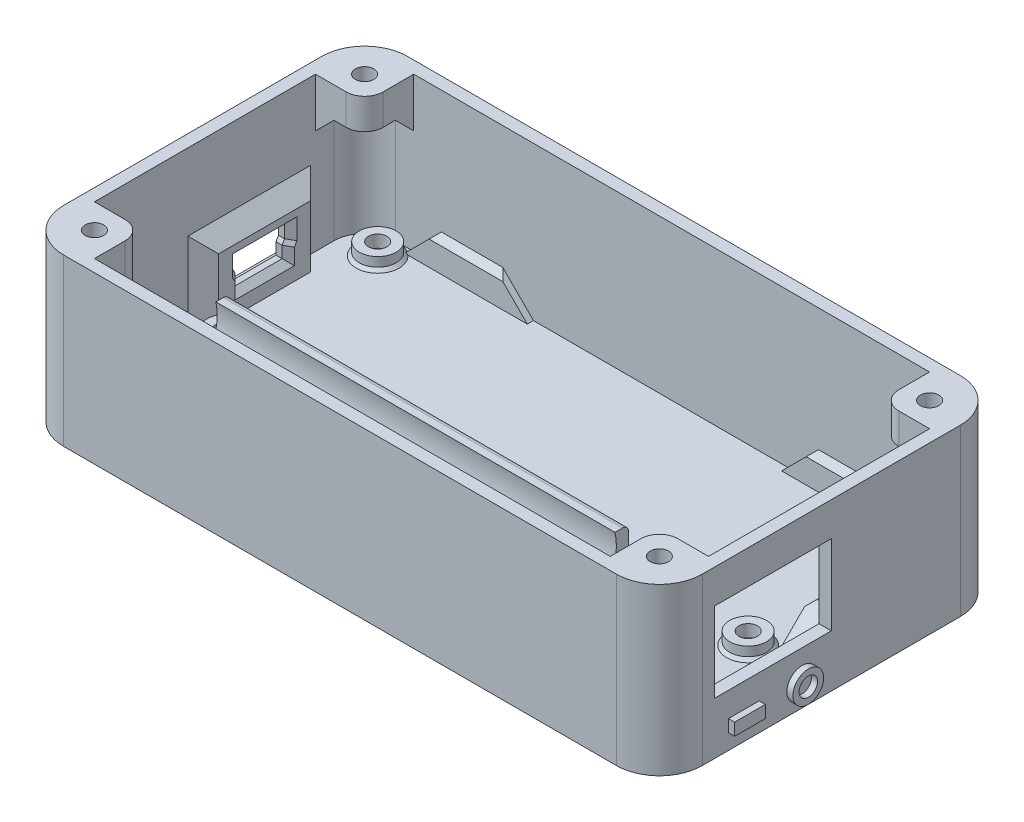
SolidWorks part; units mm, degrees
ref_plane "Front Plane" through (0, 0, 0) normal (0, 0, 1) x (1, 0, 0)
ref_plane "Top Plane" through (0, 0, 0) normal (0, 1, 0) x (1, 0, 0)
ref_plane "Right Plane" through (0, 0, 0) normal (1, 0, 0) x (0, 0, -1)
sketch "Sketch1" plane through (0, 0, 0) normal (0, 1, 0) x (1, 0, 0)
  line L0 (-45, 28) -> (45, 28)
  line L1 (-45, -26) -> (45, -26)
  line L2 (-50, -21) -> (-50, 21)
  line L3 (-45, 26) -> (45, 26)
  line L4 (50, -21) -> (50, 21)
  line L5 (-50, -26) -> (50, 26) construction
  line L6 (-50, 26) -> (50, -26) construction
  line L7 (52, -21) -> (52, 21)
  line L8 (-45, -28) -> (45, -28)
  line L9 (-52, -21) -> (-52, 21)
  arc A0 (-50, -21) -> (-45, -26) centre (-45, -21) ccw
  arc A1 (50, -21) -> (45, -26) centre (45, -21) cw
  arc A2 (50, 21) -> (45, 26) centre (45, 21) ccw
  arc A3 (-45, 26) -> (-50, 21) centre (-45, 21) ccw
  arc A4 (52, 21) -> (45, 28) centre (45, 21) ccw
  arc A5 (52, -21) -> (45, -28) centre (45, -21) cw
  arc A6 (-52, -21) -> (-45, -28) centre (-45, -21) ccw
  arc A7 (-45, 28) -> (-52, 21) centre (-45, 21) ccw
  point P0 (0, 0)
  dimension "D3" = 5
  dimension "D1" = 100
  dimension "D2" = 52
  dimension "D4" = 2
extrude "Boss-Extrude1" add sketch "Sketch1" along normal blind 2 contours L9 A7 L0 A4 L7 A5 L8 A6
extrude "Boss-Extrude2" add sketch "Sketch1<3>" along normal blind 27
sketch "Sketch1<3>" plane through (0, 0, 0) normal (0, 1, 0) x (1, 0, 0) same geometry as "Sketch1"
sketch "Sketch2" plane through (-52, 0, 0) normal (-1, 0, 0) x (0, 0, 1)
  line L0 (-28, 2) -> (28, 2) construction
  line L1 (-28, 27) -> (-28, 0) construction
  line L2 (28, 27) -> (28, 0) construction
  line L3 (21, 0) -> (-21, 0) construction
  line L4 (-28, 5.6) -> (28, 5.6) construction
  line L5 (-26, 0) -> (-26, 27) construction
  line L6 (-28, 0) -> (-21, 0) construction
  line L7 (-21, 27) -> (-28, 27) construction
  line L8 (-11.07, 7.9) -> (-3.37, 7.9) construction
  line L9 (-11.07, 5.6) -> (-3.37, 5.6) construction
  line L10 (-11.07, 5.6) -> (-11.07, 9.5) construction
  line L11 (-11.07, 9.5) -> (-3.37, 9.5) construction
  line L12 (-3.37, 5.6) -> (-3.37, 9.5) construction
  line L13 (-11.07, 5.6) -> (-3.37, 9.5) construction
  line L14 (-11.07, 9.5) -> (-3.37, 5.6) construction
  line L19 (-3.77, 5.6) -> (-10.67, 5.6) construction
  line L20 (-3.77, 5.6) -> (-3.77, 9.5) construction
  line L21 (-3.77, 9.5) -> (-10.67, 9.5) construction
  line L22 (-10.67, 5.6) -> (-10.67, 9.5) construction
  line L23 (-3.77, 5.6) -> (-10.67, 9.5) construction
  line L24 (-3.77, 9.5) -> (-10.67, 5.6) construction
  line L25 (-11.07, 7.2) -> (-3.37, 7.2) construction
  line L26 (-11.07, 9.5) -> (-11.07, 7.9) construction
  line L27 (-11.07, 7.9) -> (-10.67, 7.2) construction
  line L28 (-10.67, 7.2) -> (-10.67, 5.6) construction
  line L29 (-10.67, 5.6) -> (-3.77, 5.6) construction
  line L30 (-3.77, 5.6) -> (-3.77, 7.2) construction
  line L31 (-3.77, 7.2) -> (-3.37, 7.9) construction
  line L32 (-3.37, 7.9) -> (-3.37, 9.5) construction
  line L33 (-3.37, 9.5) -> (-11.07, 9.5) construction
  line L34 (-28, 4) -> (28, 4) construction
  line L35 (-2.97, 9.9) -> (-11.47, 9.9)
  line L36 (-11.47, 9.9) -> (-11.47, 7.7938)
  line L37 (-11.47, 7.7938) -> (-11.07, 7.0938)
  line L38 (-11.07, 7.0938) -> (-11.07, 5.2)
  line L39 (-11.07, 5.2) -> (-3.37, 5.2)
  line L40 (-3.37, 5.2) -> (-3.37, 7.0938)
  line L41 (-3.37, 7.0938) -> (-2.97, 7.7938)
  line L42 (-2.97, 7.7938) -> (-2.97, 9.9)
  line L43 (-14.72, 3.05) -> (-14.72, 2)
  line L44 (0.28, 3.05) -> (-14.72, 3.05) construction
  line L45 (0.28, 3.05) -> (0.28, 12.05)
  line L46 (0.28, 12.05) -> (-14.72, 12.05)
  line L47 (-14.72, 3.05) -> (-14.72, 12.05)
  line L48 (0.28, 3.05) -> (-14.72, 12.05) construction
  line L49 (0.28, 12.05) -> (-14.72, 3.05) construction
  line L50 (-14.72, 2) -> (0.28, 2)
  line L51 (0.28, 2) -> (0.28, 3.05)
  line L52 (-14.72, 3.05) -> (0.28, 3.05)
  point P20 (-7.22, 7.55)
  point P21 (-7.22, 7.55)
  point P22 (-7.22, 7.55)
  point P43 (-7.22, 7.55)
  dimension "D1" = 2
  dimension "D3" = 2
  dimension "D4" = 7.7
  dimension "D5" = 3.9
  dimension "D6" = 6.9
  dimension "D7" = 1.6
  dimension "D8" = 1.6
  dimension "D2" = 2
  dimension "D9" = 1.6
  dimension "D10" = 18.78
  dimension "D12" = 9
  dimension "D13" = 15
  dimension "D11" = 0.4
extrude "Boss-Extrude3" add sketch "Sketch2" against normal blind 4.5 contours L52 L43 L50 L51 | L47 L52 L45 L46 L42 L41 L40 L39 L38 L37 L36 L35 region at (-52, 2.525, -7.22) region at (-52, 7.55, -14.5451)
extrude "Cut-Extrude1" cut sketch "Sketch2<2>" against normal blind 4.5 contours L41 L42 L35 L36 L37 L38 L39 L40 region at (-52, 7.6073, -7.22)
sketch "Sketch2<2>" plane through (-52, 0, 0) normal (-1, 0, 0) x (0, 0, 1) same geometry as "Sketch2"
fillet "Chamfer1" radius 2.5 3 edges at (-50, 7.025, 0.28) (-50, 12.05, -7.22) (-50, 7.025, -14.72) type face fillet profile chamfer first side face at (-48.75, 7.025, -14.72) first side face at (-48.75, 7.025, 0.28) first side face at (-48.75, 12.05, -7.22) second side face at (-50, 10.7625, -3.61)
chamfer "Chamfer2" distance 1 angle 45 8 edges at (-47.5, 8.8469, -2.97) (-47.5, 7.4438, -3.17) (-47.5, 6.1469, -3.37) (-47.5, 9.9, -7.22) (-47.5, 8.8469, -11.47) (-47.5, 7.4438, -11.27) (-47.5, 6.1469, -11.07) (-47.5, 5.2, -7.22)
extrude "Cut-Extrude3" cut sketch "Sketch2<5>" against normal blind 2.5 contours L47 L52 L45 L46 L42 L41 L40 L39 L38 L37 L36 L35 region at (-52, 7.55, -14.5451)
sketch "Sketch2<5>" plane through (-52, 0, 0) normal (-1, 0, 0) x (0, 0, 1) same geometry as "Sketch2"
sketch "Sketch3" plane through (0, 2, 0) normal (0, 1, 0) x (1, 0, 0)
  line L0 (-45, 26) -> (45, 26) construction
  line L1 (-47.5, 25) -> (43.9, 25) construction
  line L2 (-47.5, 25) -> (-47.5, -5.5) construction
  line L3 (-47.5, -5.5) -> (43.9, -5.5) construction
  line L4 (43.9, 25) -> (43.9, -5.5) construction
  line L5 (-47.5, 25) -> (43.9, -5.5) construction
  line L6 (-47.5, -5.5) -> (43.9, 25) construction
  line L8 (-50, 17.22) -> (-50, 21) construction
  line L10 (-37.5, 25) -> (-27.5, 25)
  line L11 (-37.5, 25) -> (-37.5, 26)
  line L12 (-37.5, 26) -> (-27.5, 26)
  line L13 (-27.5, 25) -> (-27.5, 26)
  line L14 (-37.5, 25) -> (-27.5, 26) construction
  line L15 (-37.5, 26) -> (-27.5, 25) construction
  line L16 (23.9, 25) -> (33.9, 25)
  line L17 (23.9, 25) -> (23.9, 26)
  line L18 (23.9, 26) -> (33.9, 26)
  line L19 (33.9, 25) -> (33.9, 26)
  line L20 (23.9, 25) -> (33.9, 26) construction
  line L21 (23.9, 26) -> (33.9, 25) construction
  line L26 (50, -21) -> (50, 21) construction
  line L27 (43.9, 4.75) -> (50, 4.75)
  line L28 (43.9, 4.75) -> (43.9, 14.75)
  line L29 (43.9, 14.75) -> (50, 14.75)
  line L30 (50, 4.75) -> (50, 14.75)
  line L31 (43.9, 4.75) -> (50, 14.75) construction
  line L32 (43.9, 14.75) -> (50, 4.75) construction
  circle A0 centre (-44.33, 22.46) radius 1.5
  circle A1 centre (40.76, 22.46) radius 1.5
  circle A2 centre (40.76, -2.31) radius 1.5
  circle A3 centre (-44.33, -2.31) radius 1.5
  circle A4 centre (-44.33, 22.46) radius 3
  circle A5 centre (-44.33, -2.31) radius 3
  circle A6 centre (40.76, -2.31) radius 3
  circle A7 centre (40.76, 22.46) radius 3
  point P4 (-1.8, 9.75)
  point P29 (-32.5, 25.5)
  point P34 (28.9, 25.5)
  point P39 (46.95, 9.75)
  line M20 (50, -21) -> (50, 21)
  dimension "D11" = 3
  dimension "D12" = 3
  dimension "D13" = 3
  dimension "D14" = 3
  dimension "D1" = 1
  dimension "D2" = 2.5
  dimension "D3" = 91.4
  dimension "D4" = 30.5
  dimension "D5" = 3.17
  dimension "D6" = 2.54
  dimension "D7" = 85.09
  dimension "D8" = 24.77
  dimension "D9" = 85.09
  dimension "D10" = 24.77
  dimension "D16" = 10
  dimension "D17" = 10
  dimension "D18" = 10
  dimension "D19" = 10
  dimension "D20" = 10
  dimension "D15" = 1.5
extrude "Boss-Extrude4" add sketch "Sketch3" along normal blind 2 contours A4 | A0 | A3 | A5 | A2 | A6 | A1 | A7
extrude "Boss-Extrude5" add sketch "Sketch3<3>" along normal blind 5 contours L29 L28 L27 M20 | L12 L13 L10 L11 | L16 L19 L18 L17 region at (46.95, 2, -9.75)
sketch "Sketch3<3>" plane through (0, 2, 0) normal (0, 1, 0) x (1, 0, 0) same geometry as "Sketch3"
chamfer "Chamfer3" distance 5 angle 45 6 edges at (46.95, 2, -4.75) (46.95, 2, -14.75) (33.9, 2, -25.5) (-37.5, 2, -25.5) (-27.5, 2, -25.5) (23.9, 2, -25.5)
chamfer "Chamfer4" distance 0.5 angle 45 4 edges at (40.76, 2, 5.31) (40.76, 2, -19.46) (-44.33, 2, -19.46) (-44.33, 2, 5.31)
chamfer "Chamfer5" distance 1 angle 45 3 edges at (-32.5, 7, -25) (43.9, 7, -9.75) (28.9, 7, -25)
ref_plane "Plane1" through (-40, 0, 0) normal (1, 0, 0) x (0, 0, -1)
sketch "Sketch7" plane through (-40, 0, 0) normal (1, 0, 0) x (0, 0, -1)
  line L0 (-26, 27) -> (-26, 2) construction
  line L1 (-21, 2) -> (-26, 2) construction
  line L2 (-0.25, 2) -> (-21, 2) construction
  line L3 (-26, 27) -> (-26, 2) construction
  line L4 (-21, 2) -> (-26, 2) construction
  line L5 (-0.25, 2) -> (-6, 2) construction
  line L7 (-12.6717, 2) -> (-26, 2)
  line L8 (-9, 2) -> (-12.6717, 2)
  line L9 (-6, 7.6667) -> (-6, 12)
  line L10 (-7, 13) -> (-8.225, 13)
  line L12 (-6, 2) -> (-12.6717, 13) construction
  line L13 (-6, 13) -> (-12.6717, 2) construction
  line L15 (-26, 11) -> (-26, 16)
  line L18 (-26, 11) -> (-23.2203, 16) construction
  line L19 (-26, 16) -> (-23.2203, 11) construction
  line L20 (-26, 2) -> (-26, 16)
  line L21 (-9, 2) -> (-7, 4.6667)
  line L22 (-9, 2) -> (-21, 2) construction
  line L23 (-24.4833, 16) -> (-26, 19)
  line L24 (-26, 19) -> (-26, 16)
  line L25 (-26, 16) -> (-24.4833, 16) construction
  arc A0 (-24.4833, 16) -> (-8.225, 13) centre (-17, 11) ccw
  arc A1 (-7, 4.6667) -> (-6, 7.6667) centre (-11, 7.6667) ccw
  arc A2 (-7, 13) -> (-6, 12) centre (-7, 12) cw
  point P10 (-9.3359, 7.5)
  point P15 (-24.6101, 13.5)
  point P21 (-6, 6)
  dimension "D1" = 18
  dimension "D9" = 5
  dimension "D10" = 1
  dimension "D2" = 9
  dimension "D3" = 9
  dimension "D4" = 20
  dimension "D5" = 11
  dimension "D6" = 5
  dimension "D7" = 3
  dimension "D8" = 4
  dimension "D11" = 3
extrude "Boss-Extrude6" add sketch "Sketch7" along normal blind 65 contours A2 L10 A0 L7 L8 L21 A1 L9 | A0 L20 L7 | A0 L15 region at (-40, 15.848, 25.5244) region at (-40, 4.0103, 23.9897) region at (-40, 6.4212, 8.6012)
fillet "Fillet1" radius 0.5 1 edges at (-7.5, 2, 9)
sketch "Sketch8" plane through (52, 0, 0) normal (1, 0, 0) x (0, 0, -1)
  line L0 (-19, 27) -> (-19, 0) construction
  line L1 (-21, 27) -> (21, 27) construction
  line L2 (-21, 0) -> (21, 0) construction
  line L3 (-21, 27) -> (-21, 0) construction
  line L4 (-19, 21.5) -> (0, 21.5)
  line L5 (-19, 21.5) -> (-19, 8.5)
  line L6 (-19, 8.5) -> (0, 8.5)
  line L7 (0, 21.5) -> (0, 8.5)
  line L8 (-19, 21.5) -> (0, 8.5) construction
  line L9 (-19, 8.5) -> (0, 21.5) construction
  line L10 (-21, 13) -> (-6.5081, 13) construction
  line L12 (-19, 3.5) -> (-9.5, 3.5) construction
  line L13 (-9.5, 3.5) -> (0, 3.5) construction
  line L14 (-9.5, 3.5) -> (-9.5, 15) construction
  line L17 (-16.75, 2.5) -> (-11.75, 2.5)
  line L18 (-16.75, 2.5) -> (-16.75, 4.5)
  line L19 (-16.75, 4.5) -> (-11.75, 4.5)
  line L20 (-11.75, 2.5) -> (-11.75, 4.5)
  line L21 (-16.75, 2.5) -> (-11.75, 4.5) construction
  line L22 (-16.75, 4.5) -> (-11.75, 2.5) construction
  circle A0 centre (-4.75, 3.5) radius 2.5
  circle A1 centre (-4.75, 3.5) radius 1.5
  point P10 (-9.5, 15)
  point P16 (-14.25, 3.5)
  point P19 (-4.75, 3.5)
  point P24 (-14.25, 3.5)
  dimension "D7" = 5
  dimension "D1" = 2
  dimension "D2" = 19
  dimension "D3" = 13
  dimension "D4" = 2
  dimension "D6" = 5
  dimension "D8" = 5
  dimension "D10" = 13
  dimension "D11" = 2
  dimension "D12" = 2
  dimension "D5" = 1
extrude "Cut-Extrude4" cut sketch "Sketch8" against normal blind 2 contours L7 L4 L5 L6 region at (52, 15, 9.5)
extrude "Boss-Extrude8" add sketch "Sketch8<4>" along normal blind 1 contours A0 A1 | L20 L19 L18 L17 region at (52, 3.5, 7.1793)
sketch "Sketch8<4>" plane through (52, 0, 0) normal (1, 0, 0) x (0, 0, -1) same geometry as "Sketch8"
sketch "Sketch10" plane through (0, 27, 0) normal (0, 1, 0) x (1, 0, 0)
  line L0 (-52, 21) -> (-52, -21) construction
  line L1 (45, 28) -> (-45, 28) construction
  line L2 (-45, 26) -> (-42.5, 26) construction
  line L3 (-50, 17.22) -> (-50, 21) construction
  line L4 (-52, 21) -> (-52, -21) construction
  line L5 (45, 28) -> (-45, 28) construction
  line L6 (-45, 26) -> (-42.5, 26) construction
  line L7 (-50, 17.22) -> (-50, 21) construction
  line L8 (-50, 21) -> (-50, 18) construction
  line L9 (-42, 28) -> (-52, 28) construction
  line L10 (-42, 28) -> (-42, 18) construction
  line L11 (-42, 18) -> (-52, 18) construction
  line L12 (-52, 28) -> (-52, 18) construction
  line L13 (-42, 28) -> (-52, 18) construction
  line L14 (-42, 18) -> (-52, 28) construction
  line L15 (-50, 18) -> (-45, 18) construction
  line L16 (-42, 21) -> (-42, 26) construction
  line L17 (-42.5, 26) -> (-37.5, 26) construction
  line L18 (-42, 26) -> (-45, 26) construction
  line L19 (0, 28) -> (0, -28) construction
  line L20 (-50, 21) -> (-50, 18)
  line L21 (-50, 18) -> (-45, 18)
  line L22 (-45, -28) -> (45, -28) construction
  line L23 (-42, 21) -> (-42, 26)
  line L24 (-42, 26) -> (-45, 26)
  line L25 (50, 18) -> (45, 18)
  line L26 (50, 21) -> (50, 18)
  line L27 (42, 26) -> (45, 26)
  line L28 (42, 21) -> (42, 26)
  line L29 (-14.85, 0) -> (14.85, 0) construction
  line L30 (50, -21) -> (50, -18)
  line L31 (42, -26) -> (45, -26)
  line L32 (42, -21) -> (42, -26)
  line L33 (50, -18) -> (45, -18)
  line L34 (-50, -18) -> (-45, -18)
  line L35 (-50, -21) -> (-50, -18)
  line L36 (-42, -26) -> (-45, -26)
  line L37 (-42, -21) -> (-42, -26)
  arc A0 (-45, 28) -> (-52, 21) centre (-45, 21) ccw construction
  arc A1 (-45, 26) -> (-50, 21) centre (-45, 21) ccw construction
  arc A2 (-45, 28) -> (-52, 21) centre (-45, 21) ccw construction
  arc A3 (-45, 26) -> (-50, 21) centre (-45, 21) ccw construction
  arc A4 (-45, 18) -> (-42, 21) centre (-45, 21) ccw construction
  circle A5 centre (-46, 22) radius 1.5
  arc A6 (-50, 21) -> (-45, 26) centre (-45, 21) cw
  arc A7 (-45, 18) -> (-42, 21) centre (-45, 21) ccw
  circle A8 centre (46, 22) radius 1.5
  arc A9 (50, 21) -> (45, 26) centre (45, 21) ccw
  arc A10 (45, 18) -> (42, 21) centre (45, 21) cw
  circle A11 centre (46, -22) radius 1.5
  arc A12 (50, -21) -> (45, -26) centre (45, -21) cw
  arc A13 (45, -18) -> (42, -21) centre (45, -21) ccw
  circle A14 centre (-46, -22) radius 1.5
  arc A15 (-50, -21) -> (-45, -26) centre (-45, -21) ccw
  arc A16 (-45, -18) -> (-42, -21) centre (-45, -21) cw
  point P14 (-47, 23)
  line M21 (-50, -21) -> (-50, 21)
  arc M22 (-50, 21) -> (-45, 26) centre (-45, 21) cw
  line M23 (-45, 26) -> (45, 26)
  arc M24 (45, 26) -> (50, 21) centre (45, 21) cw
  line M25 (50, 21) -> (50, -21)
  dimension "D3" = 3
  dimension "D4" = 3
  dimension "D1" = 10
  dimension "D2" = 10
  dimension "D5" = 4
  dimension "D6" = 4
extrude "Boss-Extrude9" add sketch "Sketch10" against normal blind 5 contours L21 A7 L23 A5 M23 M22 M21 | A10 L25 L28 A8 M25 M24 M23 | L32 L31 A12 L30 L33 A13 | A11 region at (-48.4555, 27, -24.4555) region at (43.5, 27, -25.8869)
extrude "Boss-Extrude10" add sketch "Sketch10<3>" against normal up to surface (25 mm away) contours A15 L36 L37 A16 L34 L35 | A14 up to face at (-2.1919, 2, -6.5216)
sketch "Sketch10<3>" plane through (0, 27, 0) normal (0, 1, 0) x (1, 0, 0) same geometry as "Sketch10"
chamfer "Chamfer7" distance 3 angle 45 6 edges at (50, 22, 19.5) (43.5, 22, 26) (43.5, 22, -26) (50, 22, -19.5) (-50, 22, -19.5) (-43.5, 22, -26)
chamfer "Chamfer8" distance 2 angle 45 4 edges at (-40, 2, 21.5) (-40, 2, 12.5) (25, 2, 21.5) (25, 2, 12.5)
